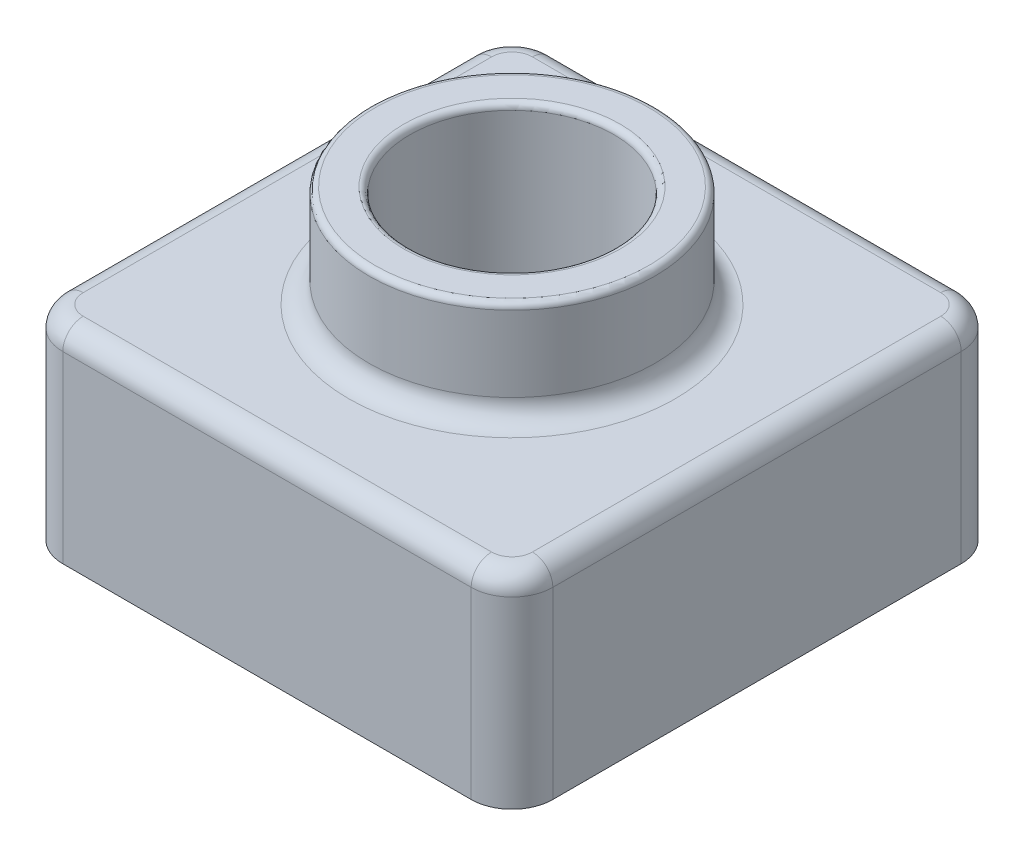
SolidWorks part; units mm, degrees
material "Chrome Stainless Steel"
ref_plane "Front Plane" through (0, 0, 0) normal (0, 0, 1) x (1, 0, 0)
ref_plane "Top Plane" through (0, 0, 0) normal (0, 1, 0) x (1, 0, 0)
ref_plane "Right Plane" through (0, 0, 0) normal (1, 0, 0) x (0, 0, -1)
sketch "Sketch1" plane through (0, 0, 0) normal (0, 1, 0) x (1, 0, 0)
  line L1 (-60, 60) -> (60, 60)
  line L2 (-60, 60) -> (-60, -60)
  line L3 (-60, -60) -> (60, -60)
  line L4 (60, 60) -> (60, -60)
  line L5 (-60, 60) -> (60, -60) construction
  line L6 (-60, -60) -> (60, 60) construction
  point P0 (0, 0)
  dimension "D1" = 120
extrude "Boss-Extrude1" add sketch "Sketch1" along normal blind 50
sketch "Sketch2" plane through (0, 50, 0) normal (0, 1, 0) x (1, 0, 0)
  circle A0 centre (0, 0) radius 35
  dimension "D1" = 70
extrude "Boss-Extrude2" add sketch "Sketch2" along normal blind 25
sketch "Sketch3" plane through (0, 75, 0) normal (0, 1, 0) x (1, 0, 0)
  circle A0 centre (0, 0) radius 25
  circle A1 centre (0, 0) radius 35
  circle A2 centre (0, 0) radius 35
  dimension "D1" = 0
  dimension "D2" = 10
extrude "Cut-Extrude3" cut sketch "Sketch3" against normal through all contours A0 region at (0, 75, 0)
fillet "Fillet1" radius 5 5 edges at (0, 50, 35) (0, 50, 60) (-60, 50, 0) (0, 50, -60) (60, 50, 0)
fillet "Fillet3" radius 10 8 edges at (58.5355, 48.5355, 58.5355) (58.5355, 48.5355, -58.5355) (-58.5355, 48.5355, -58.5355) (-58.5355, 48.5355, 58.5355) (-60, 22.5, 60) (-60, 22.5, -60) (60, 22.5, -60) (60, 22.5, 60)
fillet "Fillet2" radius 1.5 2 edges at (0, 75, 35) (0, 75, 25)
shell "Shell1" thickness 2 removed face at (0, 0, 25)
